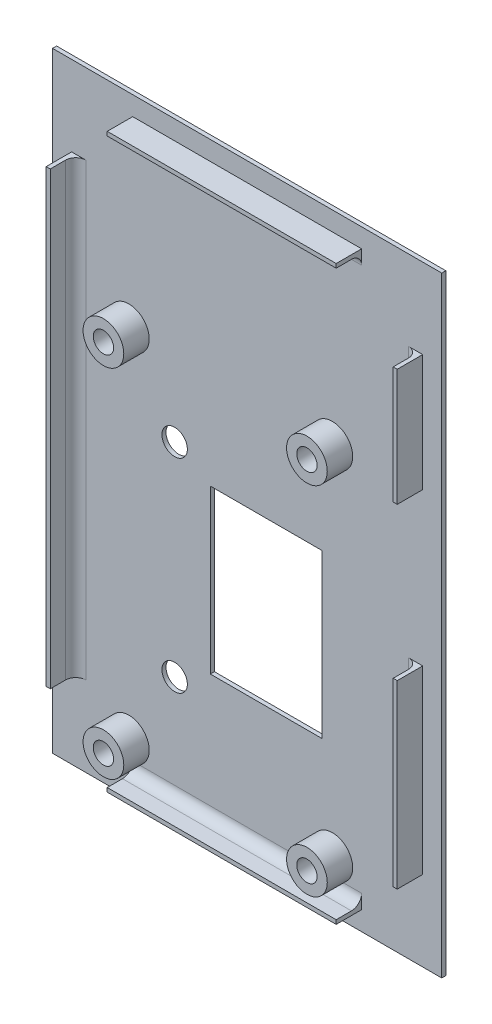
SolidWorks part; units mm, degrees
ref_plane "正面" through (0, 0, 0) normal (0, 0, 1) x (1, 0, 0)
ref_plane "平面" through (0, 0, 0) normal (0, 1, 0) x (1, 0, 0)
ref_plane "右側面" through (0, 0, 0) normal (1, 0, 0) x (0, 0, -1)
sketch "ｽｹｯﾁ1" plane through (0, 0, 0) normal (0, 0, 1) x (1, 0, 0)
  line L1 (0, 0) -> (76.5, 0)
  line L2 (0, 0) -> (0, 120)
  line L3 (0, 120) -> (76.5, 120)
  line L4 (76.5, 0) -> (76.5, 120)
  dimension "D1" = 76.5
  dimension "D2" = 120
extrude "ﾎﾞｽ - 押し出し1" add sketch "ｽｹｯﾁ1" along normal blind 0.8
sketch "ｽｹｯﾁ2" plane through (0, 0, 0.8) normal (0, 0, 1) x (1, 0, 0)
  line L0 (0, 0) -> (76.5, 0) construction
  line L1 (10, 85) -> (60, 85) construction
  line L2 (10, 85) -> (10, 5) construction
  line L3 (10, 5) -> (60, 5) construction
  line L4 (60, 85) -> (60, 5) construction
  line L6 (10, 10) -> (60, 10) construction
  line L7 (55, 5) -> (55, 85) construction
  line L8 (60, 80) -> (10, 80) construction
  line L9 (15, 85) -> (15, 5) construction
  line L10 (24, 85) -> (24, 5) construction
  line L35 (10, 25) -> (60, 25) construction
  line L36 (10, 65) -> (60, 65) construction
  line L38 (0, 120) -> (0, 0) construction
  line L39 (10, 45) -> (60, 45) construction
  line L40 (35, 85) -> (35, 5) construction
  line L41 (76.5, 45) -> (0, 45) construction
  line L44 (76.5, 0) -> (76.5, 120) construction
  line L45 (0, 120) -> (0, 0) construction
  dimension "D1" = 50
  dimension "D2" = 80
  dimension "D3" = 45
  dimension "D4" = 10
  dimension "D5" = 5
  dimension "D6" = 5
  dimension "D7" = 5
  dimension "D8" = 5
  dimension "D13" = 14
  dimension "D14" = 20
  dimension "D15" = 20
sketch "ｽｹｯﾁ5" plane through (0, 0, 0.8) normal (0, 0, 1) x (1, 0, 0)
  line L1 (10, 65) -> (60, 65) construction
  line L2 (24, 85) -> (24, 5) construction
  line L3 (10, 25) -> (60, 25) construction
  circle A4 centre (24, 65) radius 2.5
  circle A5 centre (24, 25) radius 2.5
  dimension "D5" = 5
  dimension "D6" = 5
extrude "ｶｯﾄ - 押し出し2" cut sketch "ｽｹｯﾁ5" against normal through all
sketch "ｽｹｯﾁ7" plane through (0, 0, 0.8) normal (0, 0, 1) x (1, 0, 0)
  line L0 (15, 85) -> (15, 5) construction
  line L1 (10, 10) -> (60, 10) construction
  line L2 (55, 5) -> (55, 85) construction
  line L3 (60, 80) -> (10, 80) construction
  circle A0 centre (55, 80) radius 4
  circle A1 centre (15, 80) radius 4
  circle A2 centre (55, 10) radius 4
  circle A3 centre (15, 10) radius 4
  circle A4 centre (15, 80) radius 2
  circle A5 centre (55, 80) radius 2
  circle A6 centre (55, 10) radius 2
  circle A7 centre (15, 10) radius 2
  dimension "D1" = 8
  dimension "D2" = 8
  dimension "D3" = 8
  dimension "D4" = 8
  dimension "D5" = 4
  dimension "D6" = 4
  dimension "D7" = 4
  dimension "D8" = 4
extrude "ﾎﾞｽ - 押し出し2" add sketch "ｽｹｯﾁ7" along normal blind 5
sketch "ｽｹｯﾁ8" plane through (0, 0, 0.8) normal (0, 0, 1) x (1, 0, 0)
  line L0 (60, 85) -> (60, 5) construction
  line L1 (31, 61) -> (53, 61)
  line L2 (31, 61) -> (31, 29)
  line L3 (31, 29) -> (53, 29)
  line L4 (53, 61) -> (53, 29)
  line L5 (10, 5) -> (60, 5) construction
  dimension "D1" = 7
  dimension "D2" = 24
  dimension "D3" = 22
  dimension "D4" = 32
extrude "ｶｯﾄ - 押し出し4" cut sketch "ｽｹｯﾁ8" against normal through all
sketch "ｽｹｯﾁ9" plane through (0, 0, 0.8) normal (0, 0, 1) x (1, 0, 0)
  circle A0 centre (15, 80) radius 2
  circle A1 centre (55, 80) radius 2
  circle A2 centre (55, 10) radius 2
  circle A3 centre (15, 10) radius 2
extrude "ｶｯﾄ - 押し出し5" cut sketch "ｽｹｯﾁ9" against normal through all
sketch "ｽｹｯﾁ10" plane through (0, 0, 0.8) normal (0, 0, 1) x (1, 0, 0)
  line L0 (0, 120) -> (0, 0) construction
  line L5 (72.75, 3.75) -> (3.75, 3.75)
  line L6 (72.75, 3.75) -> (72.75, 116.25)
  line L7 (72.75, 116.25) -> (3.75, 116.25)
  line L8 (3.75, 3.75) -> (3.75, 116.25)
  line L9 (0, 0) -> (76.5, 0) construction
  line L10 (76.5, 0) -> (76.5, 120) construction
  line L11 (76.5, 120) -> (0, 120) construction
  line L13 (71.95, 4.55) -> (4.55, 4.55)
  line L14 (71.95, 4.55) -> (71.95, 115.45)
  line L15 (71.95, 115.45) -> (4.55, 115.45)
  line L16 (4.55, 4.55) -> (4.55, 115.45)
  dimension "D1" = 3.75
  dimension "D2" = 3.75
  dimension "D3" = 3.75
  dimension "D4" = 3.75
  dimension "D5" = 0.8
  dimension "D6" = 0.8
  dimension "D7" = 0.8
  dimension "D8" = 0.8
extrude "ﾎﾞｽ - 押し出し4" add sketch "ｽｹｯﾁ10" along normal blind 5
sketch "ｽｹｯﾁ11" plane through (0, 0, 5.8) normal (0, 0, 1) x (1, 0, 0)
  line L21 (71.95, 51.25) -> (72.75, 51.25)
  line L49 (71.95, 51.25) -> (71.95, 81.25)
  line L76 (71.95, 81.25) -> (72.75, 81.25)
  line L77 (72.75, 51.25) -> (72.75, 81.25)
  line L95 (3.75, 116.25) -> (15.75, 116.25)
  line L104 (72.75, 116.25) -> (3.75, 116.25) construction
  line L105 (15.75, 116.25) -> (15.75, 115.45)
  line L106 (71.95, 115.45) -> (4.55, 115.45) construction
  line L107 (15.75, 115.45) -> (4.55, 115.45)
  line L108 (4.55, 115.45) -> (4.55, 4.55) construction
  line L109 (4.55, 115.45) -> (4.55, 104.25)
  line L110 (4.55, 104.25) -> (3.75, 104.25)
  line L111 (3.75, 116.25) -> (3.75, 3.75) construction
  line L112 (3.75, 104.25) -> (3.75, 116.25)
  line L113 (72.75, 104.25) -> (72.75, 116.25)
  line L114 (72.75, 3.75) -> (72.75, 116.25) construction
  line L115 (72.75, 116.25) -> (60.75, 116.25)
  line L116 (60.75, 116.25) -> (60.75, 115.45)
  line L117 (60.75, 115.45) -> (71.95, 115.45)
  line L118 (71.95, 115.45) -> (71.95, 104.25)
  line L119 (71.95, 4.55) -> (71.95, 115.45) construction
  line L120 (71.95, 104.25) -> (72.75, 104.25)
  line L121 (72.75, 3.75) -> (72.75, 15.75)
  line L122 (72.75, 15.75) -> (71.95, 15.75)
  line L123 (71.95, 15.75) -> (71.95, 4.55)
  line L124 (71.95, 4.55) -> (60.75, 4.55)
  line L125 (4.55, 4.55) -> (71.95, 4.55) construction
  line L126 (60.75, 4.55) -> (60.75, 3.75)
  line L127 (3.75, 3.75) -> (72.75, 3.75) construction
  line L128 (60.75, 3.75) -> (72.75, 3.75)
  line L129 (3.75, 3.75) -> (15.75, 3.75)
  line L130 (15.75, 3.75) -> (15.75, 4.55)
  line L131 (15.75, 4.55) -> (4.55, 4.55)
  line L132 (4.55, 4.55) -> (4.55, 15.75)
  line L133 (4.55, 15.75) -> (3.75, 15.75)
  line L134 (3.75, 15.75) -> (3.75, 3.75)
  dimension "D1" = 12
  dimension "D2" = 12
  dimension "D3" = 12
  dimension "D4" = 12
  dimension "D5" = 12
  dimension "D6" = 12
  dimension "D7" = 12
  dimension "D8" = 12
  dimension "D9" = 35
  dimension "D10" = 30
extrude "ｶｯﾄ - 押し出し6" cut sketch "ｽｹｯﾁ11" against normal up to surface (5 mm away) up to face at (38.25, 60, 0.8)
sketch "ｽｹｯﾁ12" plane through (0, 0, 0) normal (0, 0, -1) x (-1, 0, 0)
  line L0 (-76.5, 120) -> (0, 120) construction
  line L1 (-76.5, 0) -> (-72.5, 0)
  line L2 (-76.5, 0) -> (-76.5, 120)
  line L3 (-76.5, 120) -> (-72.5, 120)
  line L4 (-72.5, 0) -> (-72.5, 120)
  dimension "D1" = 4
extrude "ｶｯﾄ - 押し出し7" [suppressed] cut sketch "ｽｹｯﾁ12" against normal up to next
fillet "ﾌｨﾚｯﾄ1" radius 2 5 edges at (4.55, 60, 0.8) (38.25, 4.55, 0.8) (71.95, 33.5, 0.8) (71.95, 92.75, 0.8) (38.25, 115.45, 0.8)
